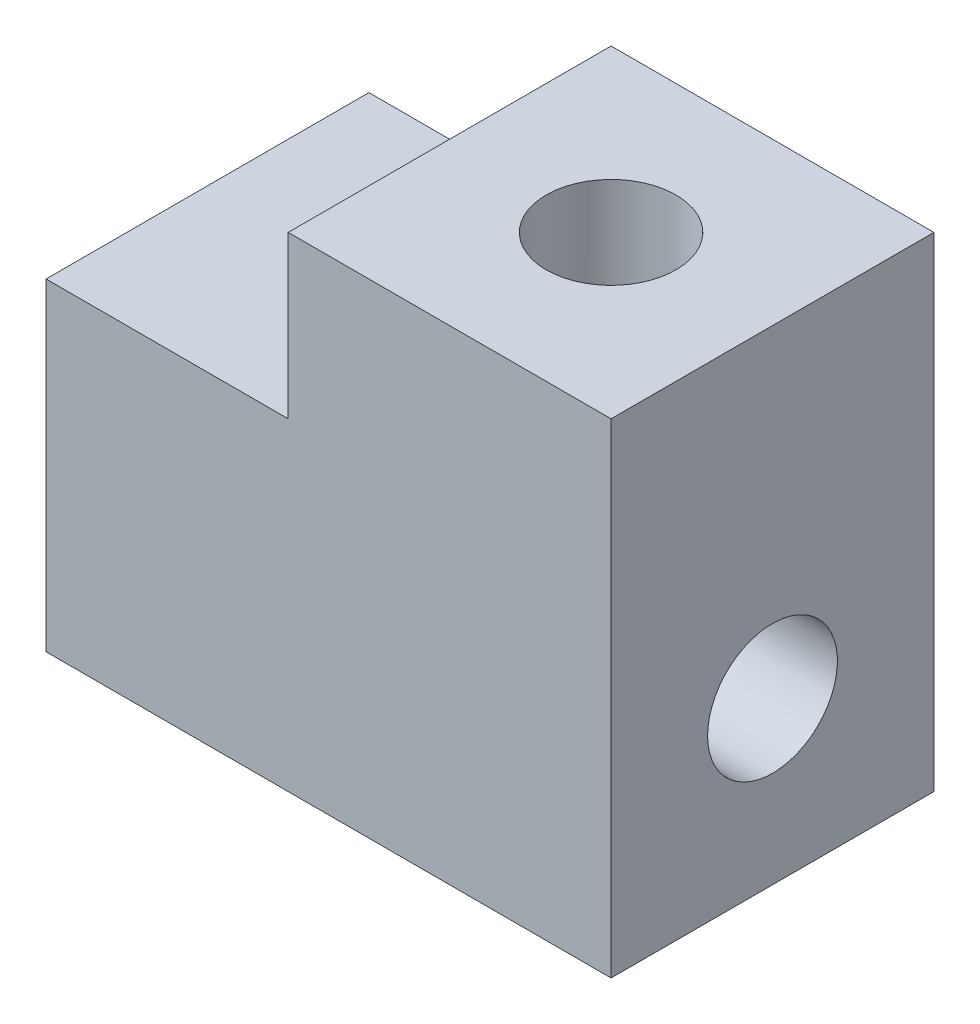
SolidWorks part; units mm, degrees
material "6061-T6 (SS)"
ref_plane "Front" through (0, 0, 0) normal (0, 0, 1) x (1, 0, 0)
ref_plane "Top" through (0, 0, 0) normal (0, 1, 0) x (1, 0, 0)
ref_plane "Right" through (0, 0, 0) normal (1, 0, 0) x (0, 0, -1)
sketch "Sketch1" plane through (0, 0, 0) normal (0, 0, 1) x (1, 0, 0)
  line L0 (0, 0) -> (0, 19.05)
  line L1 (0, 19.05) -> (-12.7, 19.05)
  line L2 (-12.7, 19.05) -> (-12.7, 12.7)
  line L3 (-12.7, 12.7) -> (-22.225, 12.7)
  line L4 (-22.225, 12.7) -> (-22.225, 0)
  line L5 (-22.225, 0) -> (0, 0)
  dimension "D1" = 12.7
  dimension "D2" = 12.7
  dimension "D3" = 19.05
  dimension "D4" = 22.225
extrude "Boss-Extrude1" add sketch "Sketch1" along normal blind 12.7
hole_wizard "1/4-20 Tapped Hole1" positions "Sketch2" profile "Sketch3" tap size "1/4-20" standard "ANSI Inch" end condition through all
sketch "Sketch2" plane through (0, 19.05, 0) normal (0, 1, 0) x (1, 0, 0)
  line L0 (-12.7, 0) -> (0, -12.7) construction
  point P0 (-6.35, -6.35)
sketch "Sketch3" plane through (-6.35, 19.05, 6.35) normal (1, 0, 0) x (0, 0, 1)
  line L0 (0, 0) -> (0, 19.05)
  line L1 (0, 19.05) -> (2.5527, 19.05)
  line L2 (2.5527, 19.05) -> (2.5527, 0)
  line L5 (2.5527, 0) -> (0, 0)
  line L11 (0, -6.35) -> (0, 107.95) construction
  dimension "Thru Tap Drill Dia." = 5.1054
  dimension "Thru Tap Drill Depth" = 19.05
cosmetic thread "Hole Thread1" parameters "D2"=6.35
hole_wizard "1/4-20 Tapped Hole2" positions "Sketch4" profile "Sketch5" tap size "1/4-20" standard "ANSI Inch" end condition through all
sketch "Sketch4" plane through (-22.225, 0, 0) normal (-1, 0, 0) x (0, 0, 1)
  line L0 (0, 12.7) -> (12.7, 0) construction
  point P0 (6.35, 6.35)
cosmetic thread "Hole Thread2" parameters "D2"=6.35
sketch "Sketch5" plane through (-22.225, 6.35, 6.35) normal (0, 1, 0) x (0, 0, 1)
  line L0 (0, 0) -> (0, 22.225)
  line L1 (0, 22.225) -> (2.5527, 22.225)
  line L2 (2.5527, 22.225) -> (2.5527, 0)
  line L5 (2.5527, 0) -> (0, 0)
  line L11 (0, -6.35) -> (0, 107.95) construction
  dimension "Thru Tap Drill Dia." = 5.1054
  dimension "Thru Tap Drill Depth" = 22.225
